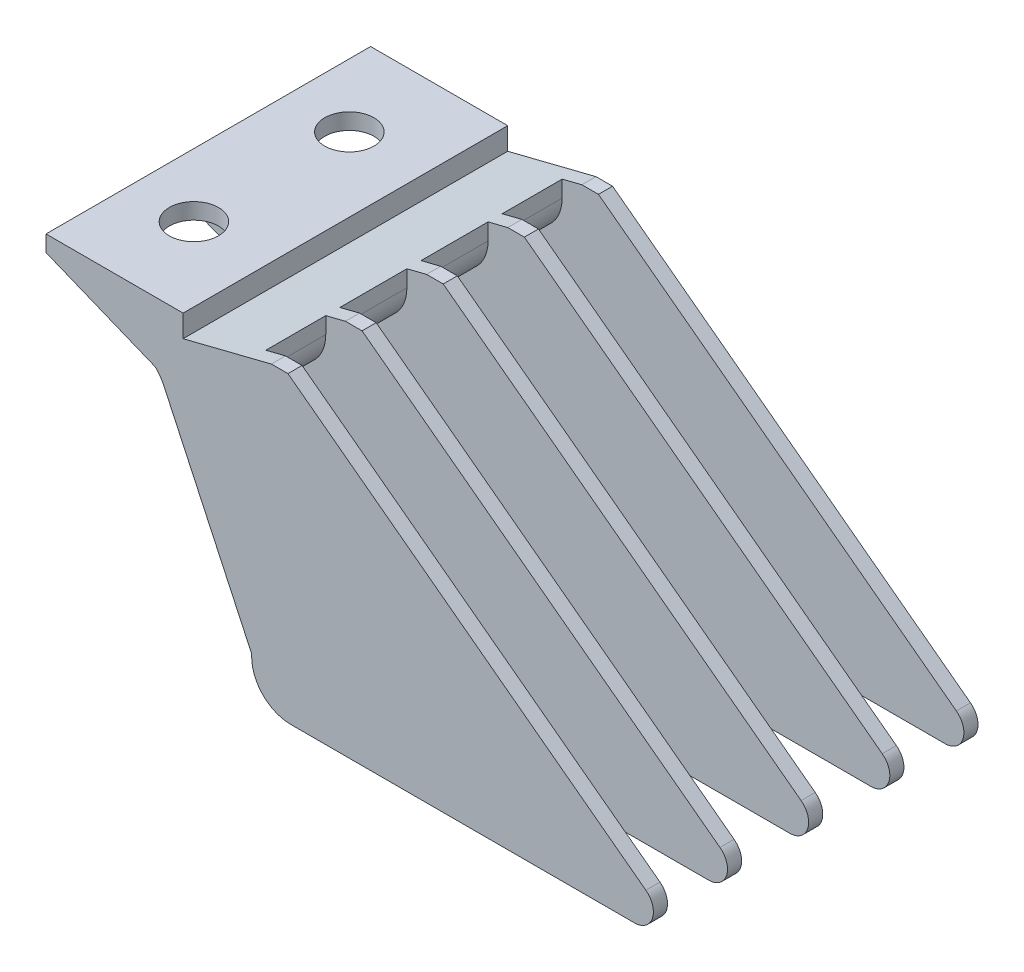
SolidWorks part; units mm, degrees
ref_plane "Front Plane" through (0, 0, 0) normal (0, 0, 1) x (1, 0, 0)
ref_plane "Top Plane" through (0, 0, 0) normal (0, 1, 0) x (1, 0, 0)
ref_plane "Right Plane" through (0, 0, 0) normal (1, 0, 0) x (0, 0, -1)
sketch "Sketch1" plane through (0, 0, 0) normal (0, 0, 1) x (1, 0, 0)
  line L0 (15.24, -19.05) -> (66.04, -19.05)
  line L1 (-15.24, -19.05) -> (15.24, -19.05)
  line L2 (-15.24, -19.05) -> (-15.24, 19.05)
  line L3 (-15.24, 19.05) -> (15.24, 19.05)
  line L5 (-15.24, -19.05) -> (15.24, 19.05) construction
  line L6 (-15.24, 19.05) -> (15.24, -19.05) construction
  line L8 (15.24, -19.05) -> (15.24, 19.05)
  line L11 (66.04, -19.05) -> (15.24, 19.05)
  line L12 (-15.24, 11.43) -> (10.668, 11.43)
  line L13 (10.668, 11.43) -> (10.668, -19.05)
  point P0 (0, 0)
  dimension "D1" = 30.48
  dimension "D2" = 38.1
  dimension "D3" = 50.8
  dimension "D4" = 7.62
  dimension "D5" = 4.572
extrude "Boss-Extrude1" add sketch "Sketch1" against normal blind 40.894 contours L0 L11 L8 | L1 L8 L3 L2 region at (32.1733, -6.35, 0) region at (12.954, -18.5621, 0)
sketch "Sketch2" plane through (0, 19.05, 0) normal (0, 1, 0) x (1, 0, 0)
  line L0 (-15.24, 20.447) -> (15.24, 20.447)
  line L1 (-15.24, 40.894) -> (-15.24, 0) construction
  line L2 (15.24, 40.894) -> (15.24, 0) construction
sketch "Sketch3" plane through (0, 0, -40.894) normal (0, 0, -1) x (-1, 0, 0)
  line L0 (15.24, 19.05) -> (-15.24, 19.05) construction
  line L1 (15.24, 19.05) -> (-15.24, 19.05)
  line L2 (-17.1958, 20.066) -> (-2.032, 16.256)
  line L3 (-2.032, 16.256) -> (-2.032, 19.05)
  line L4 (15.24, 11.43) -> (15.24, 19.05) construction
  line L5 (15.24, 11.43) -> (-10.668, 11.43) construction
  line L6 (15.24, 11.43) -> (15.24, 19.05)
  line L7 (15.24, 11.43) -> (-10.668, 11.43)
  line L8 (-2.032, 16.256) -> (-2.032, 11.43)
  line L9 (1.4829, 17.018) -> (15.24, 17.018)
  line L10 (1.4829, 19.05) -> (1.4829, 11.43)
  line M8 (-10.668, 11.43) -> (15.24, 11.43)
  line M9 (15.24, 11.43) -> (15.24, 19.05)
  dimension "D1" = 2.794
  dimension "D2" = 15.1638
  dimension "D3" = 75.896
  dimension "D4" = 2.032
extrude "Cut-Extrude2" cut sketch "Sketch3" against normal up to surface (40.894 mm away) contours L9 L10 M8 M9 | L2 L3 L1 region at (-8.3615, 14.224, -40.894) region at (5.7387, 18.1187, -40.894) up to face at (12.0227, 3.81, 0)
sketch "Sketch6" plane through (10.668, 0, 0) normal (-1, 0, 0) x (0, 0, 1)
  line L2 (-40.894, -19.05) -> (0, -19.05) construction
  line L4 (-40.894, 19.05) -> (0, 19.05)
  line L5 (-40.894, 19.05) -> (-40.894, -19.05)
  line L6 (-40.894, -19.05) -> (0, -19.05)
  line L7 (0, 19.05) -> (0, -19.05)
  line L8 (-39.116, -19.05) -> (-39.116, 19.05)
  line L9 (-20.447, -19.05) -> (-20.447, 19.05) construction
  line L10 (-21.336, -19.05) -> (-21.336, 19.05)
  line L11 (-20.447, 0) -> (-40.894, 0) construction
  line L12 (-30.6705, 0) -> (-30.6705, -19.05) construction
  line L13 (-31.5595, -19.05) -> (-31.5595, 19.05)
  line L14 (-29.7815, -19.05) -> (-29.7815, 19.05)
  line L15 (-1.778, -19.05) -> (-1.778, 19.05)
  line L16 (-9.3345, -19.05) -> (-9.3345, 19.05)
  line L17 (-11.1125, -19.05) -> (-11.1125, 19.05)
  line L18 (-19.558, -19.05) -> (-19.558, 19.05)
  line L19 (-40.894, 19.05) -> (0, 19.05) construction
  line L20 (-40.894, 19.05) -> (0, 19.05)
  line M12 (0, 11.43) -> (-40.894, 11.43)
  dimension "D1" = 1.778
  dimension "D2" = 0.889
  dimension "D3" = 0.889
  dimension "D4" = 0
extrude "Cut-Extrude4" cut sketch "Sketch6" against normal through all contours L6 L13 L8 M12 | L13 L4 L8 M12 | L14 L10 L4 M12 | L14 L6 L10 M12 | L18 L6 L17 M12 | L18 L17 L4 M12 | L16 L15 L4 M12 | L16 L6 L15 M12 region at (10.668, 15.24, -35.3377) region at (10.668, -3.81, -35.3377) region at (10.668, 15.24, -25.5588) region at (10.668, -3.81, -25.5588) region at (10.668, 15.24, -15.3352) region at (10.668, -3.81, -15.3352) region at (10.668, 15.24, -5.5563) region at (10.668, -3.81, -5.5563)
fillet "Fillet1" radius 2.38 5 edges at (66.04, -19.05, -0.889) (66.04, -19.05, -10.2235) (66.04, -19.05, -20.447) (66.04, -19.05, -40.005) (66.04, -19.05, -30.6705)
fillet "Fillet2" radius 4.92 5 edges at (10.668, -19.05, -0.889) (10.668, -19.05, -10.2235) (10.668, -19.05, -20.447) (10.668, -19.05, -30.6705) (10.668, -19.05, -40.005)
chamfer "Chamfer1" distance 25.24 angle 25 5 edges at (10.668, 11.43, -0.889) (10.668, 11.43, -40.005) (10.668, 11.43, -30.6705) (10.668, 11.43, -20.447) (10.668, 11.43, -10.2235) first distance on face at (10.668, -1.35, -0.889) first distance on face at (10.668, -1.35, -40.005) first distance on face at (10.668, -1.35, -30.6705) first distance on face at (10.668, -1.35, -20.447) first distance on face at (10.668, -1.35, -10.2235)
sketch "Sketch9" plane through (0, 17.018, 0) normal (0, -1, 0) x (1, 0, 0)
  line L0 (-1.4829, 0) -> (-15.24, 0) construction
  circle A2 centre (-7.2644, -30.2387) radius 2.8448 construction
  circle A3 centre (-7.2644, -10.6553) radius 2.8448 construction
  circle A4 centre (-7.2644, -10.6553) radius 3.0988
  circle A5 centre (-7.2644, -30.2387) radius 3.0988
  dimension "D3" = 5.6896
  dimension "D1" = 19.5834
  dimension "D2" = 10.6553
  dimension "D4" = 0.254
  dimension "D5" = 0.254
extrude "Cut-Extrude5" cut sketch "Sketch9" against normal through all contours A4 | A5
ref_plane "Plane4" through (0, 0, -20.447) normal (0, 0, -1) x (-1, 0, 0)
sketch "Sketch10" plane through (0, 0, -20.447) normal (0, 0, -1) x (-1, 0, 0)
  line L0 (1.4829, 17.018) -> (15.24, 17.018) construction
  line L1 (1.4829, 17.018) -> (1.4829, 11.43) construction
  line L2 (1.4829, 17.018) -> (15.24, 17.018)
  line L3 (1.4829, 17.018) -> (1.4829, 11.43)
  line L4 (15.24, 17.018) -> (1.4829, 11.43)
extrude "Boss-Extrude3" add sketch "Sketch10" along normal mid plane 10.16
sketch "Sketch11" plane through (0, 0, -40.894) normal (0, 0, -1) x (-1, 0, 0)
  line L0 (1.4829, 17.018) -> (15.24, 17.018) construction
  line L1 (1.4829, 17.018) -> (1.4829, 11.43) construction
  line L2 (1.4829, 17.018) -> (15.24, 17.018)
  line L3 (1.4829, 17.018) -> (1.4829, 11.43)
  line L4 (15.24, 17.018) -> (1.4829, 11.43)
extrude "Boss-Extrude4" add sketch "Sketch11" against normal blind 5.08
mirror "Mirror1" about plane through (0, 0, -20.447) normal (0, 0, -1) of "Boss-Extrude4"
fillet "Fillet3" radius 4.92 4 edges at (10.668, 11.43, -5.5563) (10.668, 11.43, -15.3352) (10.668, 11.43, -35.3377) (10.668, 11.43, -25.5587)
fillet "Fillet4" radius 4.92 5 edges at (-1.1016, 11.43, -0.889) (-1.1016, 11.43, -40.005) (-1.1016, 11.43, -30.6705) (-1.1016, 11.43, -20.447) (-1.1016, 11.43, -10.2235)
